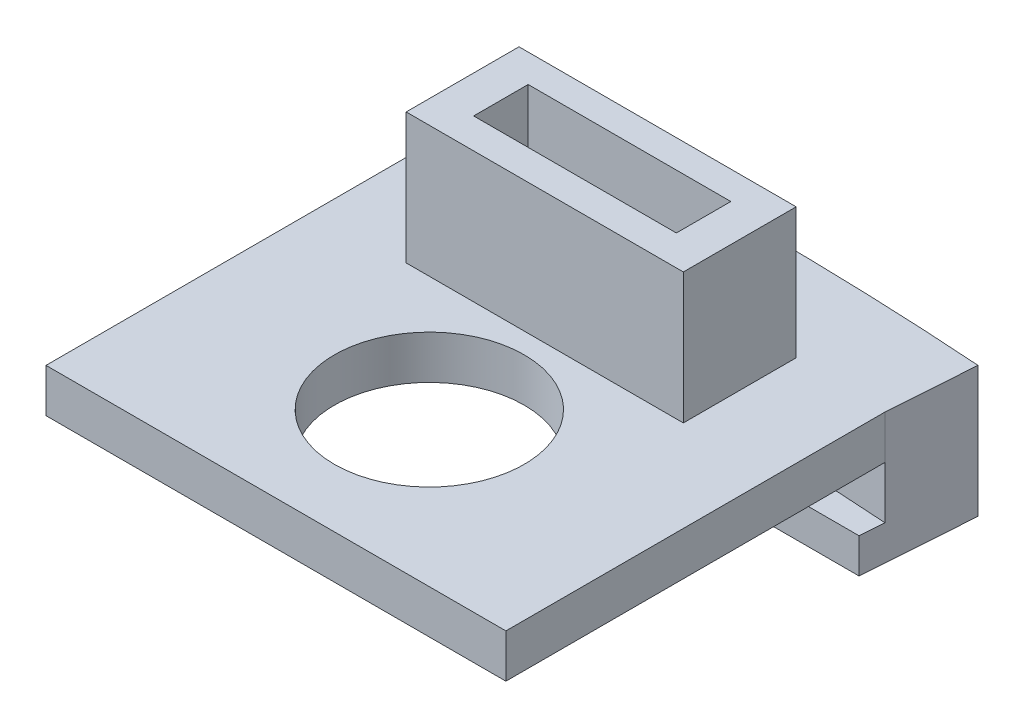
SolidWorks part; units mm, degrees
ref_plane "Front Plane" through (0, 0, 0) normal (0, 0, 1) x (1, 0, 0)
ref_plane "Top Plane" through (0, 0, 0) normal (0, 1, 0) x (1, 0, 0)
ref_plane "Right Plane" through (0, 0, 0) normal (1, 0, 0) x (0, 0, -1)
sketch "Sketch1" plane through (0, 0, 0) normal (0, 1, 0) x (1, 0, 0)
  line L0 (0, 0) -> (0, -3.6068) construction
  line L1 (-5.9055, -5.1308) -> (0, -5.1308)
  line L2 (-5.9055, -1.9558) -> (5.9055, -1.9558)
  line L3 (-13.7536, 4.5978) -> (-13.3993, -0.4679)
  line L4 (13.7536, 4.5978) -> (13.3993, -0.4679)
  line L5 (-5.9055, -1.9558) -> (-5.9055, -5.1308)
  line L6 (0, -5.1308) -> (5.9055, -5.1308)
  line L7 (5.9055, -1.9558) -> (5.9055, -5.1308)
  line L9 (-8.0751, -0.3194) -> (8.0751, -0.3194)
  line L10 (-8.0751, -0.3194) -> (-8.0751, -6.8942)
  line L13 (0, 0) -> (0, -13.6207) construction
  line L14 (-8.0751, -6.8942) -> (8.0751, -6.8942)
  line L16 (-13.3993, -0.4679) -> (-13.3993, -22.557)
  line L17 (-13.3993, -22.557) -> (13.3993, -22.557)
  line L18 (13.3993, -0.4679) -> (13.3993, -22.557)
  line L19 (8.0751, -0.3194) -> (8.0751, -6.8942)
  arc A0 (0, 0) -> (13.3993, -0.4679) centre (0, -192.0875) cw
  arc A1 (0, 0) -> (-13.3993, -0.4679) centre (0, -192.0875) ccw
  arc A2 (-13.7536, 4.5978) -> (13.7536, 4.5978) centre (0, -192.0875) cw
  circle A3 centre (0, -13.6207) radius 3.1623
  circle A4 centre (0, -13.6207) radius 5.5308
  dimension "D1" = 11.811
  dimension "D2" = 3.175
extrude "Boss-Extrude1" add sketch "Sketch1" along normal blind 2.54 contours A0 A1 L16 L17 L18 A4 L2 L7 L5 | A2 L3 A1 A0 L4 | L19 L9 L10 L14 L2 L7 L5 | L18 L16 L17 A4 | A0 A1 L16 L18 L9 L19 L14 L10 region at (0, 0, -2.392) region at (-6.7025, 0, 0.152) region at (0, 0, 0.4938)
extrude "Boss-Extrude2" add sketch "Sketch1<3>" along normal blind 10.16 contours L19 L9 L10 L14 L2 L7 L5 region at (0, 0, 0.4938)
sketch "Sketch1<3>" plane through (0, 0, 0) normal (0, 1, 0) x (1, 0, 0) same geometry as "Sketch1"
extrude "Boss-Extrude3" add sketch "Sketch1<4>" against normal blind 5.08 contours A2 L3 A1 A0 L4 region at (0, 0, -2.392)
sketch "Sketch1<4>" plane through (0, 0, 0) normal (0, 1, 0) x (1, 0, 0) same geometry as "Sketch1"
sketch "Sketch2" plane through (0, -5.08, 0) normal (0, -1, 0) x (1, 0, 0)
  line L0 (-13.7536, -4.5978) -> (-13.3993, 0.4679)
  line L1 (-13.3993, 0.4679) -> (-13.3007, 1.879)
  line L2 (13.7536, -4.5978) -> (13.3993, 0.4679)
  line L3 (13.7536, -4.5978) -> (-13.7536, -4.5978)
  line L4 (13.3993, 0.4679) -> (13.3007, 1.879)
  line L5 (-13.3007, 1.879) -> (13.3007, 1.879)
extrude "Boss-Extrude5" add sketch "Sketch2" against normal blind 2.032
sketch "Sketch3" plane through (0, 0, 0.3194) normal (0, 0, -1) x (-1, 0, 0)
  circle A0 centre (0, 12.7) radius 2.794
